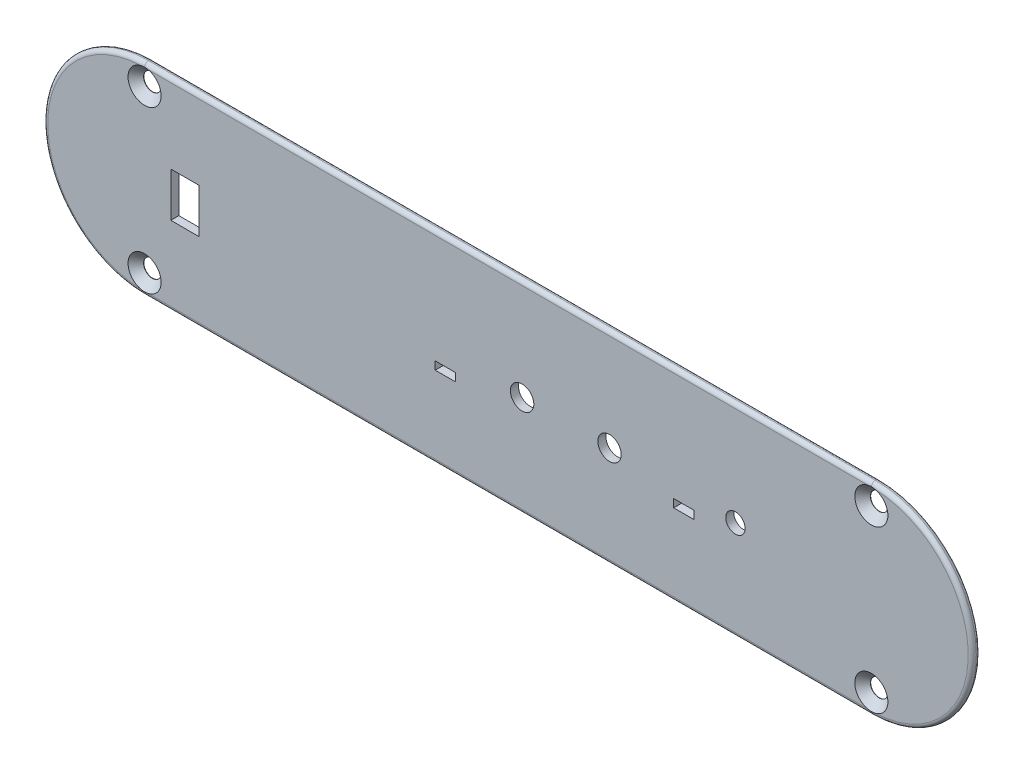
SolidWorks part; units mm, degrees
ref_plane "Front Plane" through (0, 0, 0) normal (0, 0, 1) x (1, 0, 0)
ref_plane "Top Plane" through (0, 0, 0) normal (0, 1, 0) x (1, 0, 0)
ref_plane "Right Plane" through (0, 0, 0) normal (1, 0, 0) x (0, 0, -1)
sketch "Sketch1" plane through (0, 0, 0) normal (0, 0, 1) x (1, 0, 0)
  line L0 (114.3, 0) -> (-114.3, 0) construction
  line L1 (114.3, -31.75) -> (-114.3, -31.75)
  line L2 (114.3, 31.75) -> (-114.3, 31.75)
  arc A0 (114.3, -31.75) -> (114.3, 31.75) centre (114.3, 0) ccw
  arc A1 (-114.3, 31.75) -> (-114.3, -31.75) centre (-114.3, 0) ccw
  point P2 (0, 0)
  point P8 (-146.05, 0)
  point P9 (146.05, 0)
  point P10 (0, 31.75)
  point P11 (0, -31.75)
  dimension "D2" = 292.1
  dimension "D1" = 63.5
extrude "Boss-Extrude1" add sketch "Sketch1" along normal blind 2.54
sketch "Sketch2" plane through (0, 0, 2.54) normal (0, 0, 1) x (1, 0, 0)
  line L1 (-106.045, -6.985) -> (-97.155, -6.985)
  line L2 (-106.045, -6.985) -> (-106.045, 6.985)
  line L3 (-106.045, 6.985) -> (-97.155, 6.985)
  line L4 (-97.155, -6.985) -> (-97.155, 6.985)
  line L5 (-101.6, 6.985) -> (-101.6, -6.985) construction
  line L6 (-106.045, 0) -> (-97.155, 0) construction
  line L7 (114.3, 31.75) -> (-114.3, 31.75) construction
  point P0 (-101.6, 0)
  dimension "D1" = 8.89
  dimension "D2" = 13.97
  dimension "D3" = 101.6
  dimension "D4" = 31.75
extrude "Cut-Extrude1" cut sketch "Sketch2" against normal blind 7.62
sketch "Sketch3" plane through (0, 0, 2.54) normal (0, 0, 1) x (1, 0, 0)
  line L0 (-97.155, -6.985) -> (-97.155, 6.985) construction
  line L1 (-114.3, -31.75) -> (114.3, -31.75) construction
  circle A0 centre (4.445, 0) radius 3.683
  dimension "D1" = 7.366
  dimension "D2" = 101.6
  dimension "D3" = 31.75
extrude "Cut-Extrude2" cut sketch "Sketch3" against normal blind 7.62 contours A0
pattern_linear "LPattern1" count 2 spacing 27.5 along (1, 0, 0) of "Cut-Extrude2"
sketch "Sketch4" plane through (0, 0, 2.54) normal (0, 0, 1) x (1, 0, 0)
  circle A0 centre (71.545, -0.635) radius 3.048
  circle A1 centre (31.945, 0) radius 3.683 construction
  point P2 (0, 0)
  dimension "D1" = 6.096
  dimension "D2" = 39.6
  dimension "D3" = 0.635
extrude "Cut-Extrude3" cut sketch "Sketch4" against normal blind 7.62
sketch "Sketch5" plane through (0, 0, 2.54) normal (0, 0, 1) x (1, 0, 0)
  circle A0 centre (-114.3, 25.4) radius 2.5
  dimension "D1" = 5
  dimension "D2" = 6.35
  dimension "D3" = 114.3
  dimension "D4" = 25.4
sketch "Sketch6" plane through (0, 0, 2.54) normal (0, 0, 1) x (1, 0, 0)
  line L1 (52.114, -6.223) -> (58.464, -6.223)
  line L2 (52.114, -6.223) -> (52.114, -3.683)
  line L3 (52.114, -3.683) -> (58.464, -3.683)
  line L4 (58.464, -6.223) -> (58.464, -3.683)
  line L5 (55.289, -3.683) -> (55.289, -6.223) construction
  line L6 (52.114, -4.953) -> (58.464, -4.953) construction
  circle A0 centre (71.545, -0.635) radius 3.048 construction
  point P0 (55.289, -4.953)
  dimension "D4" = 3.048
  dimension "D1" = 6.35
  dimension "D2" = 2.54
  dimension "D3" = 16.256
extrude "Cut-Extrude5" cut sketch "Sketch6" against normal blind 2.54
fillet "Fillet1" radius 1.27 8 edges at (0, -31.75, 2.54) (-146.05, 0, 2.54) (0, 31.75, 2.54) (146.05, 0, 2.54) (146.05, 0, 0) (0, -31.75, 0) (-146.05, 0, 0) (0, 31.75, 0)
hole_wizard "CSK for M5 Flat Head Machine Screw2" positions "3DSketch2" profile "Sketch9" countersink size "M5" standard "ANSI Metric" end condition through all
sketch3d "3DSketch2"
  point P0 (-114.3, 25.4, 2.54)
  point P4 (-114.3, 25.4, 2.54)
sketch "Sketch9" plane through (-114.3, 25.4, 2.54) normal (1, 0, 0) x (0, -1, 0)
  line L0 (0, 0) -> (0, 2.54)
  line L1 (0, 2.54) -> (2.75, 2.54)
  line L2 (2.75, 2.54) -> (2.75, 2.45)
  line L3 (2.75, 2.45) -> (5.2, 0)
  line L5 (5.2, 0) -> (0, 0)
  line L6 (-2.75, 2.45) -> (-5.2, 0) construction
  line L11 (0, -6.35) -> (0, 107.95) construction
  dimension "Thru Hole Dia." = 5.5
  dimension "Thru Hole Depth" = 2.54
  dimension "Near C'Sink Dia." = 10.4
  dimension "Near C'Sink Angle" = 90
pattern_linear "LPattern4" count 2 spacing 228.6 along (1, 0, 0) count 2 spacing 50.8 along (0, -1, 0) of "CSK for M5 Flat Head Machine Screw2"
pattern_linear "LPattern5" count 2 spacing 75 along (-1, 0, 0) of "Cut-Extrude5"
